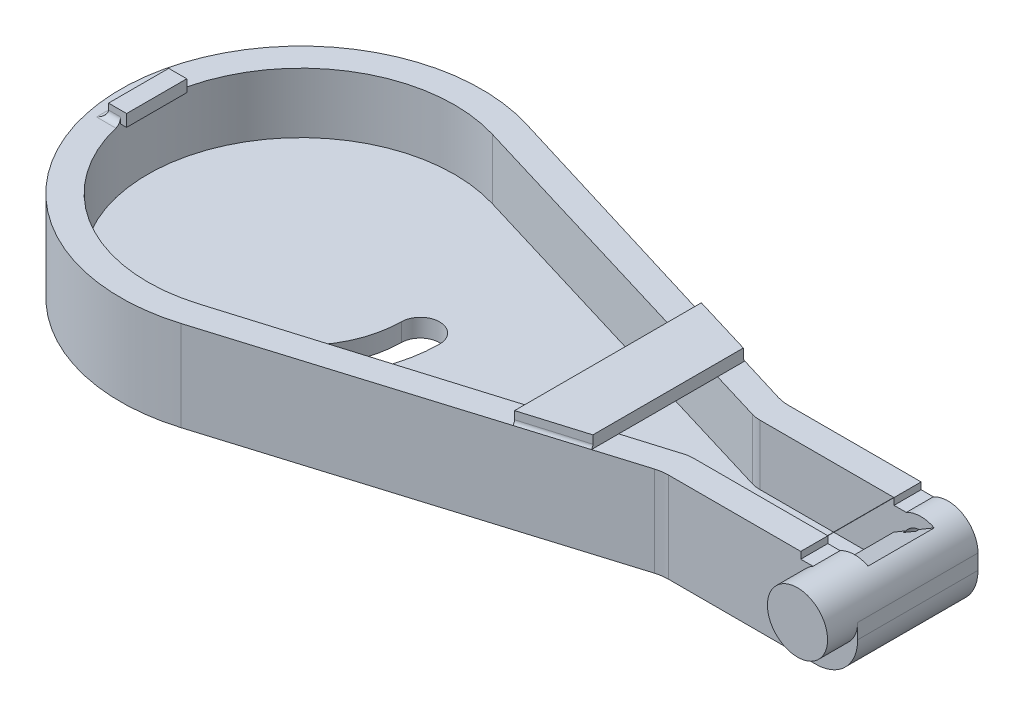
SolidWorks part; units mm, degrees
material "ABS"
ref_plane "前基準面" through (0, 0, 0) normal (0, 0, 1) x (1, 0, 0)
ref_plane "上基準面" through (0, 0, 0) normal (0, 1, 0) x (1, 0, 0)
ref_plane "右基準面" through (0, 0, 0) normal (1, 0, 0) x (0, 0, -1)
sketch "草圖1" plane through (0, 0, 0) normal (0, 1, 0) x (1, 0, 0)
  line L1 (-17.5, -10) -> (17.5, -10)
  line L2 (-17.5, -10) -> (-17.5, 10)
  line L3 (-17.5, 10) -> (17.5, 10)
  line L4 (17.5, -10) -> (17.5, 10)
  line L5 (-17.5, -10) -> (17.5, 10) construction
  line L6 (-17.5, 10) -> (17.5, -10) construction
  point P0 (0, 0)
  dimension "D1" = 35
  dimension "D2" = 20
extrude "填料-伸長1" add sketch "草圖1" along normal blind 10 and the other way blind 5
sketch "草圖6" plane through (0, 10, 0) normal (0, 1, 0) x (1, 0, 0)
  line L0 (-17.5, 10) -> (-17.5, -10) construction
  line L1 (-17.5, 5.5) -> (5.5, 5.5)
  line L2 (-17.5, 5.5) -> (-17.5, -5.5)
  line L3 (-17.5, -5.5) -> (5.5, -5.5)
  line L4 (5.5, 5.5) -> (5.5, -5.5)
  line L5 (-1000, 0) -> (49000, 0) construction
  line L6 (17.5, -10) -> (17.5, 10) construction
  dimension "D1" = 11
  dimension "D2" = 12
extrude "除料-伸長2" cut sketch "草圖6" against normal blind 10
sketch "草圖17" plane through (0, 0, 10) normal (0, 0, 1) x (1, 0, 0)
  line L0 (17.5, -5) -> (17.5, 10) construction
  circle A1 centre (10, 4.5) radius 5
  dimension "D1" = 10
  dimension "D2" = 7.5
extrude "填料-伸長3" add sketch "草圖17" along normal blind 5
sketch "草圖7" plane through (0, 0, -10) normal (0, 0, 1) x (1, 0, 0)
  line L1 (17.5, 10) -> (17.5, -5) construction
  line L6 (13, 4.5) -> (49022, 4.5) construction
  circle A0 centre (10, 4.5) radius 3
  dimension "D1" = 6
  dimension "D2" = 7.5
extrude "除料-伸長7" cut sketch "草圖7" against normal mid plane 10
sketch "草圖12" plane through (0, 0, 0) normal (0, 0, 1) x (1, 0, 0)
  line L0 (15, 4.5) -> (15, -5)
  line L1 (15, -5) -> (17.5465, -5)
  line L2 (7.5817, 8.8763) -> (5.5465, 8.8763)
  line L4 (5.5465, 8.8763) -> (5.5465, 10.4978)
  line L5 (5.5465, 10.4978) -> (17.5465, 10.4978)
  line L6 (17.5465, 10.4978) -> (17.5465, -5)
  arc A0 (15, 4.5) -> (7.5817, 8.8763) centre (10, 4.5) ccw
  dimension "D1" = 10
  dimension "D2" = 12
extrude "除料-伸長12" cut sketch "草圖12" against normal through all both and the other way through all
sketch "草圖14" plane through (0, -5, 0) normal (0, 1, 0) x (1, 0, 0)
  line L0 (-17.5, 10) -> (-78.7419, 28.6931)
  line L1 (-78.7419, -28.6931) -> (-17.5, -10)
  line L2 (-17.5, 10) -> (-17.5, -10)
  arc A0 (-78.7419, 28.6931) -> (-78.7419, -28.6931) centre (-87.5, 0) ccw
  dimension "D1" = 30
  dimension "D2" = 70
extrude "填料-伸長2" add sketch "草圖14" along normal blind 15
sketch "草圖15" plane through (0, 10, 0) normal (0, 1, 0) x (1, 0, 0)
  line L0 (-17.5, 5.5) -> (-80.1287, 24.4114)
  line L1 (-80.1287, -24.4114) -> (-17.5, -5.5)
  arc A0 (-80.1287, 24.4114) -> (-80.1287, -24.4114) centre (-87.5, 0) ccw
  line M3 (-17.5, -5.5) -> (-17.5, 5.5)
  dimension "D1" = 25.5
extrude "除料-伸長13" cut sketch "草圖15" against normal blind 10 and the other way through all contours L0 A0 L1 M3 region at (-72.0624, 10, 0)
sketch "草圖16" plane through (0, 0, 0) normal (0, 1, 0) x (1, 0, 0)
  line L0 (-87.5, 0) -> (-67.5008, -0.1745) construction
  line L1 (-87.5, 0) -> (-71.6329, -12.1752) construction
  line L2 (-1000, 0) -> (49000, 0) construction
  circle A2 centre (-87.5, 0) radius 20 construction
  arc A5 (-70.7006, -0.1466) -> (-74.1717, -10.2272) centre (-87.5, 0) cw
  arc A6 (-64.3009, -0.2025) -> (-69.0942, -14.1233) centre (-87.5, 0) cw
  arc A8 (-70.7006, -0.1466) -> (-64.3009, -0.2025) centre (-67.5008, -0.1745) cw
  arc A9 (-74.1717, -10.2272) -> (-69.0942, -14.1233) centre (-71.6329, -12.1752) ccw
  dimension "D1" = 3.2
  dimension "D2" = 3.2
  dimension "D3" = 40
  dimension "D4" = 37
  dimension "3.2" = 3.2
  dimension "D6" = 0.5
extrude "除料-伸長14" cut sketch "草圖16" against normal blind 3 contours A5 region at (-69.0987, 0, 6.3361)
fillet "圓角1" radius 7 3 edges at (15, -5, 0) (-17.5, 2.5, -10) (-17.5, 2.5, 10)
fillet "圓角2" radius 5 2 edges at (-17.5, 5, 5.5) (-17.5, 5, -5.5)
sketch "草圖18" plane through (0, 0, 0) normal (0, 0, 1) x (1, 0, 0)
  line L0 (4.7081, 9.9978) -> (13.9664, 9.9978)
  line L1 (13.9664, 9.9978) -> (4.7081, 4.5325)
  line L3 (4.7081, 4.5325) -> (4.7081, 9.9978)
extrude "除料-伸長15" cut sketch "草圖18" against normal mid plane 11
sketch "草圖19" plane through (0, 10, 0) normal (0, 1, 0) x (1, 0, 0)
  line L1 (-26.5, 12.5) -> (-36.5, 15.5196)
  line L2 (-26.5, 12.5) -> (-26.5, -12.5)
  line L3 (-26.5, -12.5) -> (-36.5, -15.5196)
  line L4 (-36.5, 15.5196) -> (-36.5, -15.5196)
  line L5 (-1000, 0) -> (1011.012, 0) construction
  line L6 (-114.5, 5) -> (-111.5, 5)
  line L7 (-114.5, 5) -> (-114.5, -5)
  line L8 (-114.5, -5) -> (-111.5, -5)
  line L9 (-111.5, 5) -> (-111.5, -5)
  line L10 (-18.2069, 5.7135) -> (-80.1287, 24.4114) construction
  arc A1 (-78.7419, 28.6931) -> (-78.7419, -28.6931) centre (-87.5, 0) ccw construction
  dimension "D1" = 3
  dimension "D2" = 24
  dimension "D3" = 10
  dimension "D4" = 26.5
  dimension "D5" = 10
  dimension "D6" = 25
extrude "填料-伸長4" add sketch "草圖19" along normal blind 2
fillet "圓角3" radius 1 5 edges at (-113.5025, 10, -5) (-113.5025, 10, 5) (-114.5, 10, 0) (-31.5, 10, -14.0098) (-31.5, 10, 14.0098)
sketch "草圖20" plane through (0, -5, 0) normal (0, -1, 0) x (1, 0, 0)
  line L9 (-19.9587, 5.5228) -> (-19.9587, -5.5228)
  line L11 (-19.9587, -5.5228) -> (-80.2016, -23.9109)
  line L12 (-80.2016, 23.9109) -> (-19.9587, 5.5228)
  line L13 (-19.9587, -5.5228) -> (-80.2016, -23.9109)
  line L14 (-80.2016, 23.9109) -> (-19.9587, 5.5228)
  arc A6 (-80.2016, 23.9109) -> (-80.2016, -23.9109) centre (-87.5, 0) ccw
  arc A7 (-80.2016, 23.9109) -> (-80.2016, -23.9109) centre (-87.5, 0) ccw
  dimension "D1" = 5
extrude "除料-伸長16" cut sketch "草圖20" against normal blind 2
